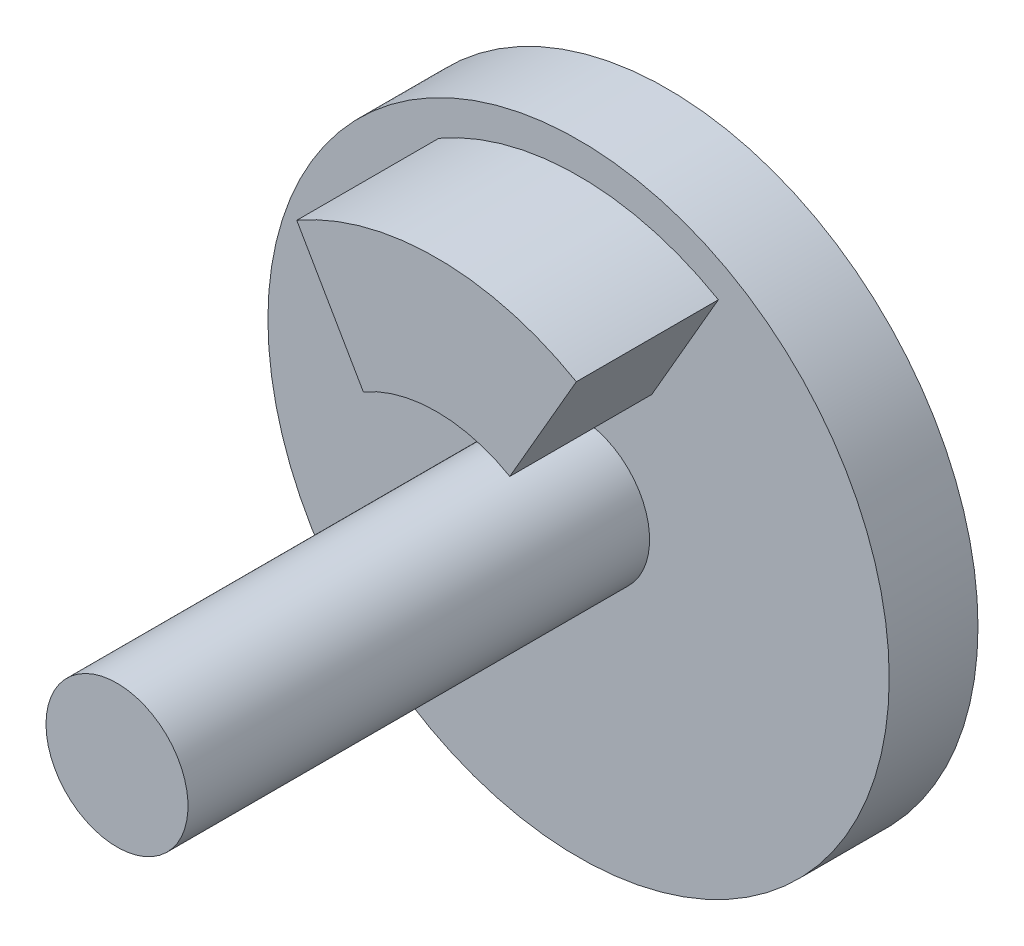
SolidWorks part; units mm, degrees
ref_plane "Front Plane" through (0, 0, 0) normal (0, 0, 1) x (1, 0, 0)
ref_plane "Top Plane" through (0, 0, 0) normal (0, 1, 0) x (1, 0, 0)
ref_plane "Right Plane" through (0, 0, 0) normal (1, 0, 0) x (0, 0, -1)
sketch "Sketch1" plane through (0, 0, 0) normal (0, 0, 1) x (1, 0, 0)
  circle A0 centre (0, 0) radius 17.5
  dimension "D1" = 35
extrude "Boss-Extrude1" add sketch "Sketch1" along normal mid plane 5
sketch "Sketch2" plane through (0, 0, 2.5) normal (0, 0, 1) x (1, 0, 0)
  line L3 (0, 0) -> (0, 11) construction
  line L4 (7.875, 13.6399) -> (4.125, 7.1447)
  line L5 (-4.125, 7.1447) -> (-7.875, 13.6399)
  arc A1 (4.125, 7.1447) -> (-4.125, 7.1447) centre (0, 0) ccw
  arc A6 (-7.875, 13.6399) -> (7.875, 13.6399) centre (0, 0) cw
  circle A7 centre (0, 0) radius 17.5 construction
  dimension "D2" = 7.5
  dimension "D3" = 1.75
  dimension "D1" = 30
extrude "Boss-Extrude2" add sketch "Sketch2" along normal blind 8
sketch "Sketch3" plane through (0, 0, 2.5) normal (0, 0, 1) x (1, 0, 0)
  circle A0 centre (0, 0) radius 4
extrude "Boss-Extrude3" add sketch "Sketch3" along normal blind 26
sketch "Sketch4" plane through (0, 0, -2.5) normal (0, 0, -1) x (-1, 0, 0)
  circle A3 centre (0, 0) radius 3
extrude "Boss-Extrude4" add sketch "Sketch4" along normal blind 10
